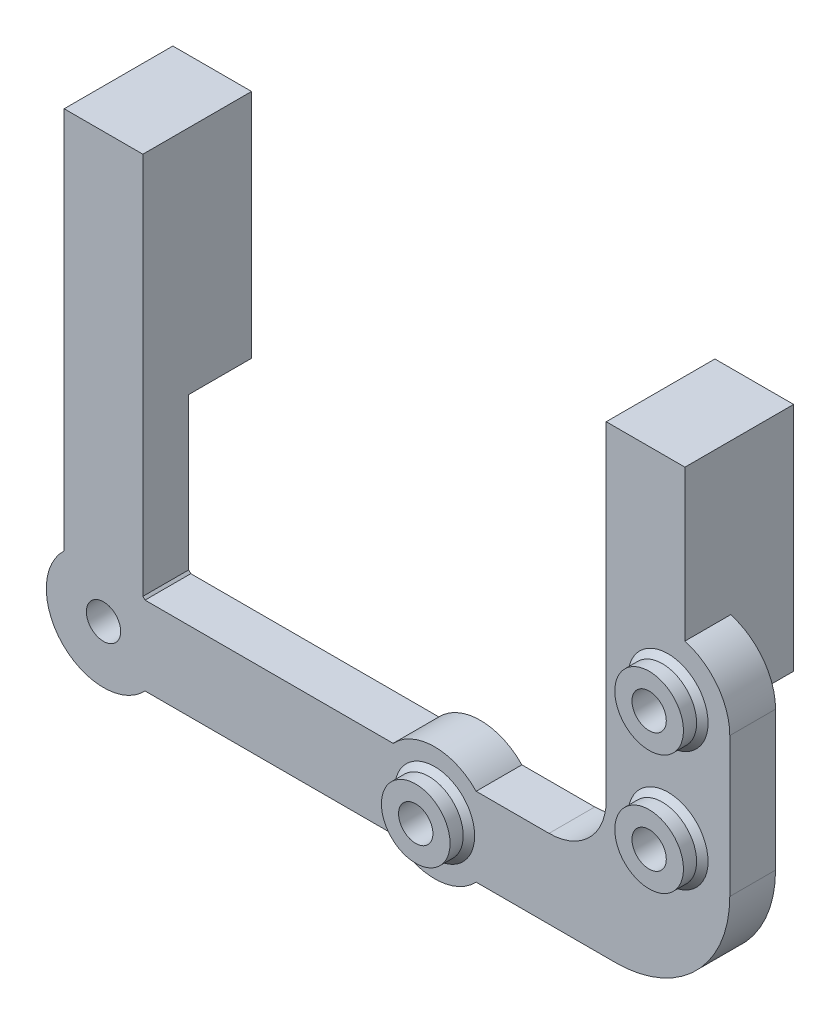
SolidWorks part; units mm, degrees
ref_plane "Alzado" through (0, 0, 0) normal (0, 0, 1) x (1, 0, 0)
ref_plane "Planta" through (0, 0, 0) normal (0, 1, 0) x (1, 0, 0)
ref_plane "Vista lateral" through (0, 0, 0) normal (1, 0, 0) x (0, 0, -1)
sketch "Croquis1" plane through (0, 0, 0) normal (0, 0, 1) x (1, 0, 0)
  line L0 (25.5, -3.4) -> (45.9, -3.4) construction
  line L1 (25.5, 10.1) -> (25.5, -16.9) construction
  line L2 (45.9, 1.84) -> (45.9, -8.64) construction
  line L3 (51.3, -10.34) -> (51.3, 1.84)
  line L4 (47.38, 20.2) -> (40.5, 20.2)
  line L8 (0, 20.2) -> (-6.88, 20.2)
  line L17 (40.5, -8.46) -> (40.5, 20.2)
  line L18 (35.5, -13.46) -> (29.1286, -13.46)
  line L19 (0, 20.2) -> (0, -13.2714)
  line L20 (0.1886, -20.34) -> (21.8714, -20.34)
  line L23 (21.8714, -13.46) -> (0.1886, -13.46)
  line L24 (29.1286, -20.34) -> (41.3, -20.34)
  line L25 (47.38, 20.2) -> (47.38, 7.0332)
  line L26 (40.5, -0.7295) -> (45.9, -0.7295) construction
  line L27 (45.9, -0.7295) -> (51.3, -0.7295) construction
  line L29 (-6.88, 15.4823) -> (-6.88, 20.2) construction
  line L30 (-6.88, 20.2) -> (-6.88, -13.2714)
  circle A0 centre (45.9, 1.84) radius 1.5
  circle A1 centre (45.9, -8.64) radius 1.5
  circle A2 centre (25.5, -16.9) radius 1.5
  arc A3 (21.8714, -20.34) -> (29.1286, -20.34) centre (25.5, -16.9) ccw
  arc A4 (-6.88, -13.2714) -> (0.1886, -20.34) centre (-3.44, -16.9) ccw
  arc A7 (0.1886, -13.46) -> (0, -13.2714) centre (-3.44, -16.9) ccw
  arc A8 (29.1286, -13.46) -> (21.8714, -13.46) centre (25.5, -16.9) ccw
  circle A9 centre (-3.44, -16.9) radius 1.5
  arc A13 (40.5, -8.46) -> (35.5, -13.46) centre (35.5, -8.46) cw
  arc A14 (41.3, -20.34) -> (51.3, -10.34) centre (41.3, -10.34) ccw
  arc A15 (47.38, 7.0332) -> (51.3, 1.84) centre (45.9, 1.84) cw
  arc A16 (51.3, 1.84) -> (40.5, 1.84) centre (45.9, 1.84) ccw construction
  dimension "D4" = 3
  dimension "D5" = 3.44
  dimension "D7" = 6.88
  dimension "D9" = 10
  dimension "D11" = 10
  dimension "D8" = 5
  dimension "D1" = 10.48
  dimension "D2" = 27
  dimension "D3" = 20.4
  dimension "D12" = 3.44
extrude "Saliente-Extruir1" add sketch "Croquis1" along normal blind 4
sketch "Croquis2" plane through (0, 0, 0) normal (0, 0, -1) x (-1, 0, 0)
  line L0 (-40.5, 20.2) -> (0, 20.2) construction
  line L1 (-40.5, 20.2) -> (-47.38, 20.2)
  line L2 (-40.5, 20.2) -> (-40.5, 0)
  line L3 (-40.5, 0) -> (-47.38, 0)
  line L4 (-47.38, 20.2) -> (-47.38, 0)
  line L6 (0, 0) -> (0, 20.2)
  line L7 (0, 20.2) -> (6.88, 20.2)
  line L8 (6.88, 0) -> (6.88, 20.2)
  line L10 (-40.5, 20.2) -> (-40.5, -8.46) construction
  line L12 (0, 0) -> (6.88, 0)
  point P4 (20, 0)
  point P6 (6.88, 20.2)
extrude "Saliente-Extruir2" add sketch "Croquis2" along normal up to surface (5.5 mm away)
sketch "Croquis3" plane through (0, 0, 4) normal (0, 0, 1) x (1, 0, 0)
  circle A0 centre (25.5, -16.9) radius 1.5
  circle A1 centre (25.5, -16.9) radius 3
  circle A2 centre (45.9, 1.84) radius 3
  circle A3 centre (45.9, 1.84) radius 1.5
  circle A4 centre (45.9, -8.64) radius 3
  circle A5 centre (45.9, -8.64) radius 1.5
  dimension "D1" = 3
  dimension "D2" = 6
extrude "Saliente-Extruir3" add sketch "Croquis3" along normal up to surface (1.65 mm away)
sketch "Croquis4" plane through (0, 0, 0) normal (0, 0, -1) x (-1, 0, 0)
  circle A0 centre (-25.5, -16.9) radius 1.5
  circle A1 centre (-45.9, 1.84) radius 1.5
  circle A2 centre (-45.9, -8.64) radius 1.5
  dimension "D1" = 3
extrude "Saliente-Extruir4" add sketch "Croquis4" against normal blind 1
sketch "Croquis5" plane through (0, 0, -5.5) normal (0, 0, -1) x (-1, 0, 0)
  circle A0 centre (-45.5, 5.4) radius 1.25
  circle A1 centre (-45.5, 14.8) radius 1.25
  circle A2 centre (5, 14.8) radius 1.25
  circle A3 centre (5, 5.4) radius 1.25
  dimension "D1" = 2.5
extrude "Cortar-Extruir1" cut sketch "Croquis5" against normal blind 8
chamfer "Chaflán1" distance 0.5 angle 45 3 edges at (48.9, 1.84, 4) (48.9, -8.64, 4) (28.5, -16.9, 4)
